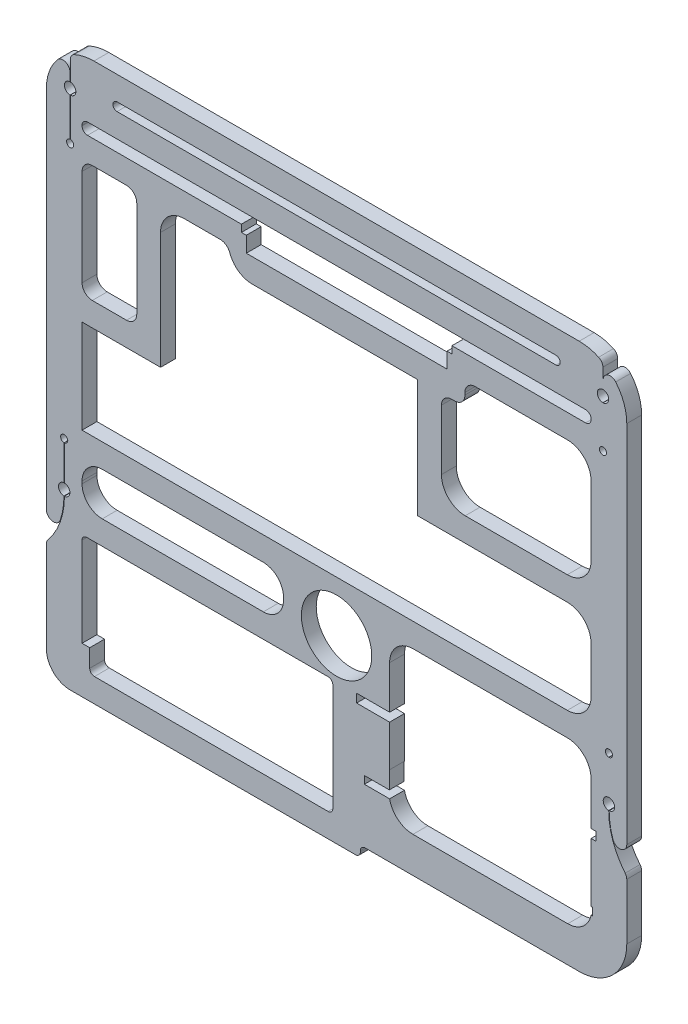
SolidWorks part; units mm, degrees
ref_plane "Front Plane" through (0, 0, 0) normal (0, 0, 1) x (1, 0, 0)
ref_plane "Top Plane" through (0, 0, 0) normal (0, 1, 0) x (1, 0, 0)
ref_plane "Right Plane" through (0, 0, 0) normal (1, 0, 0) x (0, 0, -1)
sketch "Sketch1" plane through (0, 0, 0) normal (0, 0, 1) x (1, 0, 0)
  line L0 (63.9883, 61.406) -> (63.9883, 57.596) construction
  line L1 (11.1776, 3.1158) -> (73.1542, 3.1158)
  line L2 (11.1776, 3.1158) -> (11.1776, 61.406)
  line L3 (11.1776, 61.406) -> (73.1542, 61.406)
  line L4 (73.1542, 3.1158) -> (73.1542, 61.406)
  line L5 (69.3442, 57.596) -> (14.9876, 57.596)
  line L6 (69.3442, 57.596) -> (69.3442, 6.9258)
  line L7 (69.3442, 6.9258) -> (14.9876, 6.9258)
  line L8 (14.9876, 57.596) -> (14.9876, 6.9258)
  line L9 (63.9883, 59.501) -> (18.0707, 59.501) construction
  line L10 (14.9876, 39.3805) -> (11.1776, 39.3805) construction
  line L11 (13.0826, 39.3805) -> (13.0826, 23.9527) construction
  line L12 (13.5248, 6.9258) -> (13.5248, 3.1158) construction
  line L13 (13.5248, 5.0208) -> (21.1598, 5.0208) construction
  line L14 (73.1542, 38.1916) -> (69.3442, 38.1916) construction
  line L15 (71.2492, 38.1916) -> (71.2492, 22.3321) construction
  line L16 (55.7422, 59.501) -> (30.5962, 59.501) construction
  line L19 (42.3087, 5.0208) -> (41.7626, 5.0208) construction
  line L21 (69.3442, 28.1307) -> (69.3442, 52.516) construction
  line L22 (14.9876, 47.563) -> (14.9876, 28.1307) construction
  dimension "D1" = 3.81
  dimension "D2" = 3.81
extrude "Boss-Extrude1" add sketch "Sketch1" along normal blind 1.5875
sketch "Sketch2" plane through (0, 0, 0) normal (0, 0, -1) x (-1, 0, 0)
  line L0 (-69.3442, 6.9258) -> (-69.3442, 57.596) construction
  line L1 (-69.3442, 26.6348) -> (-14.9876, 26.6348)
  line L2 (-69.3442, 26.6348) -> (-69.3442, 24.0948)
  line L3 (-69.3442, 24.0948) -> (-14.9876, 24.0948)
  line L4 (-14.9876, 26.6348) -> (-14.9876, 24.0948)
  line L5 (-14.9876, 57.596) -> (-14.9876, 6.9258) construction
  line L6 (-20.1206, 26.6348) -> (-57.8206, 26.6348) construction
  line L7 (-53.9642, 53.4304) -> (-53.9642, 51.7667)
  line L8 (-32.5266, 53.4304) -> (-32.0059, 53.4304)
  line L9 (-32.5266, 51.7667) -> (-53.9642, 51.7667) construction
  line L10 (-32.5266, 51.7667) -> (-32.5266, 53.4304) construction
  line L11 (-69.3442, 54.1924) -> (-54.4849, 54.1924)
  line L12 (-69.3442, 54.1924) -> (-69.3442, 51.6524)
  line L13 (-69.3442, 51.6524) -> (-55.8692, 51.6524)
  line L14 (-14.9876, 54.1924) -> (-14.9876, 51.6524)
  line L15 (-69.3442, 57.596) -> (-14.9876, 57.596)
  line L16 (-69.3442, 57.596) -> (-69.3442, 55.4243)
  line L17 (-69.3442, 55.4243) -> (-14.9876, 55.4243)
  line L18 (-14.9876, 57.596) -> (-14.9876, 55.4243)
  line L19 (-69.3442, 57.596) -> (-14.9876, 57.596) construction
  line L20 (-54.4849, 54.1924) -> (-54.4849, 53.4304)
  line L21 (-62.3462, 55.4243) -> (-23.9922, 55.4243) construction
  line L22 (-54.4849, 53.4304) -> (-53.9642, 53.4304)
  line L23 (-32.5266, 51.7667) -> (-53.9642, 51.7667)
  line L24 (-32.5266, 51.7667) -> (-32.5266, 53.4304)
  line L25 (-55.8692, 51.6524) -> (-55.8692, 49.2267)
  line L26 (-55.8692, 49.2267) -> (-30.6216, 49.2267)
  line L27 (-30.6216, 49.2267) -> (-30.6216, 51.6524)
  line L28 (-30.6216, 51.6524) -> (-14.9876, 51.6524)
  line L29 (-32.0059, 53.4304) -> (-32.0059, 54.1924)
  line L30 (-62.3462, 54.1924) -> (-23.9922, 54.1924) construction
  line L32 (-54.4849, 53.4304) -> (-54.4849, 54.1924) construction
  line L33 (-32.0059, 53.4304) -> (-54.4849, 53.4304) construction
  line L34 (-32.0059, 54.1924) -> (-14.9876, 54.1924)
  line L36 (-32.0059, 53.4304) -> (-32.0059, 54.1924) construction
  line L37 (-32.5266, 51.7667) -> (-32.5266, 53.4304) construction
  dimension "D1" = 2.54
  dimension "D2" = 1.905
  dimension "D3" = 2.54
  dimension "D4" = 1.905
  dimension "D5" = 2.54
extrude "Boss-Extrude2" add sketch "Sketch2" against normal up to surface (1.5875 mm away) up to face at (42.1659, 32.2609, 1.5875)
sketch "Sketch3" plane through (0, 0, 0) normal (0, 0, -1) x (-1, 0, 0)
  line L0 (-57.8206, 36.6348) -> (-50.8206, 36.6348) construction
  line L1 (-57.8206, 36.6348) -> (-50.8206, 36.6348)
  line L2 (-57.8206, 36.6348) -> (-69.3442, 36.6348)
  line L3 (-69.3442, 26.6348) -> (-69.3442, 51.6524) construction
  line L4 (-69.3442, 36.6348) -> (-69.3442, 39.1748)
  line L5 (-69.3442, 39.1748) -> (-53.3606, 39.1748)
  line L6 (-50.8206, 28.408) -> (-50.8206, 36.6348)
  line L7 (-50.8206, 28.408) -> (-50.8206, 49.2267)
  line L8 (-55.8692, 49.2267) -> (-30.6216, 49.2267) construction
  line L9 (-50.8206, 49.2267) -> (-53.3606, 49.2267)
  line L10 (-53.3606, 49.2267) -> (-53.3606, 39.1748)
  line L11 (-23.3706, 36.6348) -> (-20.1206, 36.6348) construction
  line L12 (-23.3706, 36.6348) -> (-20.1206, 36.6348)
  line L13 (-20.1206, 36.6348) -> (-14.9876, 36.6348)
  line L14 (-14.9876, 51.6524) -> (-14.9876, 26.6348) construction
  line L15 (-14.9876, 36.6348) -> (-14.9876, 39.1748)
  line L16 (-14.9876, 39.1748) -> (-20.8306, 39.1748)
  line L17 (-20.8306, 39.1748) -> (-20.8306, 51.6524)
  line L18 (-30.6216, 51.6524) -> (-14.9876, 51.6524) construction
  line L19 (-20.8306, 51.6524) -> (-23.3706, 51.6524)
  line L20 (-23.3706, 51.6524) -> (-23.3706, 36.6348)
  line L21 (-23.3706, 36.6348) -> (-16.2412, 25.8471)
  line M22 (-69.3442, 26.6348) -> (-69.3442, 51.6524)
  line M25 (-55.8692, 49.2267) -> (-30.6216, 49.2267)
  line M27 (-30.6216, 51.6524) -> (-14.9876, 51.6524)
  line M28 (-14.9876, 51.6524) -> (-14.9876, 26.6348)
  dimension "D1" = 2.54
  dimension "D2" = 2.54
  dimension "D3" = 2.54
  dimension "D4" = 2.54
extrude "Boss-Extrude3" add sketch "Sketch3" against normal up to surface (1.5875 mm away) contours L10 L5 L2 L1 L6 L7 M25 M22 | L20 L12 L13 L16 L17 M27 M28 region at (63.5824, 36.8588, 0) region at (20.9265, 42.3962, 0) up to face at (42.8855, 53.7395, 1.5875)
sketch "Sketch4" plane through (0, 0, 0) normal (0, 0, -1) x (-1, 0, 0)
  line L0 (-69.3442, 24.0948) -> (-14.9876, 24.0948) construction
  line L1 (-47.8301, 24.0948) -> (-36.5017, 24.0948)
  line L2 (-47.8301, 24.0948) -> (-47.8301, 6.9258)
  line L3 (-47.8301, 6.9258) -> (-36.5017, 6.9258)
  line L4 (-36.5017, 24.0948) -> (-36.5017, 6.9258)
  line L5 (-14.9876, 6.9258) -> (-69.3442, 6.9258) construction
  line L6 (-45.9251, 21.2246) -> (-47.8301, 21.2246) construction
  line L7 (-38.4067, 21.2246) -> (-36.5017, 21.2246) construction
  circle A0 centre (-42.1659, 21.2246) radius 3.7592 construction
  dimension "D1" = 1.905
extrude "Boss-Extrude4" add sketch "Sketch4" against normal up to surface (1.5875 mm away) up to face at (17.9091, 45.4136, 1.5875)
sketch "Sketch5" plane through (0, 0, 0) normal (0, 0, -1) x (-1, 0, 0)
  line L0 (-15.8038, 16.9715) -> (-41.7626, 16.9715) construction
  line L3 (-41.7626, 4.5128) -> (-41.7626, 16.9715) construction
  line L4 (-15.8038, 4.5128) -> (-41.7626, 4.5128) construction
  line L5 (-15.8038, 4.5128) -> (-15.8038, 16.9715) construction
  line L6 (-15.8038, 16.9715) -> (-41.7626, 16.9715)
  line L7 (-41.7626, 4.5128) -> (-41.7626, 16.9715)
  line L8 (-15.8038, 4.5128) -> (-41.7626, 4.5128)
  line L9 (-15.8038, 4.5128) -> (-15.8038, 16.9715)
  circle A0 centre (-42.1659, 21.2246) radius 3.7592 construction
  circle A1 centre (-42.1659, 21.2246) radius 3.7592
extrude "Cut-Extrude1" cut sketch "Sketch5" against normal up to surface (1.5875 mm away) up to face at (58.5871, 15.5103, 1.5875)
sketch "Sketch8" plane through (0, 0, 0) normal (0, 0, -1) x (-1, 0, 0)
  line L1 (-36.5017, 16.9715) -> (-14.9876, 16.9715)
  line L2 (-36.5017, 16.9715) -> (-36.5017, 19.5115)
  line L3 (-36.5017, 19.5115) -> (-14.9876, 19.5115)
  line L4 (-14.9876, 16.9715) -> (-14.9876, 19.5115)
  line L5 (-14.9876, 24.0948) -> (-14.9876, 6.9258) construction
  dimension "D1" = 2.54
extrude "Boss-Extrude5" add sketch "Sketch8" against normal up to surface (1.5875 mm away) up to face at (38.4067, 21.2246, 1.5875)
fillet "Fillet1" radius 5.08 3 edges at (73.1542, 3.1158, 0.7937) (11.1776, 61.406, 0.7937) (73.1542, 61.406, 0.7937)
fillet "Fillet2" radius 2.54 7 edges at (23.3706, 51.6524, 0.7937) (30.6216, 49.2267, 0.7937) (69.3442, 51.6524, 0.7937) (53.3606, 39.1748, 0.7937) (69.3442, 26.6348, 0.7937) (69.3442, 39.1748, 0.7937) (69.3442, 36.6348, 0.7937)
fillet "Fillet3" radius 1.0922 8 edges at (53.3606, 49.2267, 0.7937) (55.8692, 49.2267, 0.7937) (55.8692, 51.6524, 0.7937) (14.9876, 39.1748, 0.7937) (20.8306, 39.1748, 0.7937) (14.9876, 51.6524, 0.7937) (20.8306, 51.6524, 0.7937) (30.6216, 51.6524, 0.7937)
fillet "Fillet4" radius 0.5842 4 edges at (14.9876, 55.4243, 0.7937) (69.3442, 55.4243, 0.7937) (69.3442, 54.1924, 0.7937) (14.9876, 54.1924, 0.7937)
fillet "Fillet8" radius 2.159 4 edges at (36.5017, 19.5115, 0.7937) (36.5017, 24.0948, 0.7937) (14.9876, 24.0948, 0.7938) (14.9876, 19.5115, 0.7937)
sketch "Sketch6" plane through (0, 0, 0) normal (0, 0, -1) x (-1, 0, 0)
  line L0 (-16.6206, 28.1348) -> (-18.1206, 26.6348) construction
  line L1 (-18.1206, 36.6348) -> (-16.6206, 35.1348) construction
  line L2 (-16.6206, 35.1348) -> (-16.6206, 28.1348) construction
  line L3 (-16.6206, 28.1348) -> (-18.1206, 26.6348)
  line L4 (-18.1206, 36.6348) -> (-16.6206, 35.1348)
  line L5 (-16.6206, 35.1348) -> (-16.6206, 28.1348)
  line L6 (-18.1206, 36.6348) -> (-18.1206, 26.6348)
  circle A0 centre (-71.2492, 20.1932) radius 0.6096 construction
  circle A1 centre (-71.2492, 20.1932) radius 0.6096
  circle A4 centre (-70.6142, 57.596) radius 0.6096 construction
  circle A5 centre (-70.6142, 57.596) radius 0.6096
  circle A6 centre (-13.0826, 20.1932) radius 0.6096 construction
  circle A7 centre (-13.0826, 20.1932) radius 0.6096
  circle A10 centre (-13.7176, 57.596) radius 0.6096 construction
  circle A11 centre (-13.7176, 57.596) radius 0.6096
extrude "Cut-Extrude2" cut sketch "Sketch6" against normal up to surface (1.5875 mm away) up to face at (24.1846, 9.4701, 1.5875)
sketch "Sketch7" plane through (0, 0, 0) normal (0, 0, -1) x (-1, 0, 0)
  line L0 (-44.3026, 16.9715) -> (-69.8804, 16.9715) construction
  line L1 (-69.8804, 16.9715) -> (-69.8804, 16.0571) construction
  line L2 (-69.8804, 16.0571) -> (-44.3026, 16.0571) construction
  line L3 (-44.3026, 16.0571) -> (-44.3026, 16.9715) construction
  line L4 (-45.1366, 9.7751) -> (-69.5206, 9.7751) construction
  line L5 (-69.5206, 9.7751) -> (-69.5206, 8.9623) construction
  line L6 (-69.5206, 8.9623) -> (-45.1366, 8.9623) construction
  line L7 (-45.1366, 8.9623) -> (-45.1366, 9.7751) construction
  line L8 (-44.3026, 16.9715) -> (-69.8804, 16.9715)
  line L9 (-69.8804, 16.9715) -> (-69.8804, 16.0571)
  line L10 (-69.8804, 16.0571) -> (-44.3026, 16.0571)
  line L11 (-44.3026, 16.0571) -> (-44.3026, 16.9715)
  line L12 (-45.1366, 9.7751) -> (-69.5206, 9.7751)
  line L13 (-69.5206, 9.7751) -> (-69.5206, 8.9623)
  line L14 (-69.5206, 8.9623) -> (-45.1366, 8.9623)
  line L15 (-45.1366, 8.9623) -> (-45.1366, 9.7751)
  line L20 (-66.8536, 9.7751) -> (-47.8036, 9.7751)
  line L21 (-47.8036, 9.7751) -> (-47.8036, 11.6547)
  line L22 (-47.8036, 11.6547) -> (-66.8536, 11.6547)
  line L23 (-66.8536, 11.6547) -> (-66.8536, 9.7751)
  line L24 (-66.8536, 9.7751) -> (-47.8036, 9.7751)
  line L25 (-47.8036, 9.7751) -> (-47.8036, 11.6547)
  line L26 (-47.8036, 11.6547) -> (-66.8536, 11.6547)
  line L27 (-66.8536, 11.6547) -> (-66.8536, 9.7751)
  dimension "D1" = 0
extrude "Cut-Extrude3" cut sketch "Sketch7" against normal up to surface (1.5875 mm away) contours L14 L15 L12 L13 | L26 L27 L12 L25 | L10 L11 L8 L9 region at (57.0915, 16.5143, 0) region at (57.3286, 9.3687, 0) region at (57.3286, 10.7149, 0) up to face at (13.108, 57.596, 1.5875)
fillet "Fillet6" radius 0.508 4 edges at (41.7626, 16.9715, 0.7937) (41.7626, 4.5128, 0.7937) (15.8038, 4.5128, 0.7937) (14.9876, 16.9715, 0.7937)
sketch "Sketch9" plane through (0, 0, 1.5875) normal (0, 0, 1) x (1, 0, 0)
  line L0 (68.0742, 61.406) -> (16.2576, 61.406) construction
  line L1 (18.2896, 58.866) -> (66.0422, 58.866)
  line L2 (18.2896, 58.866) -> (18.2896, 57.9643)
  line L3 (18.2896, 57.9643) -> (66.0422, 57.9643)
  line L8 (66.0422, 58.866) -> (66.0422, 57.9643)
  line L9 (15.5718, 55.4243) -> (68.76, 55.4243) construction
  line L10 (11.1776, 56.326) -> (11.1776, 59.3208) construction
  line L11 (18.2896, 58.866) -> (11.1776, 58.866) construction
  line L13 (66.0422, 58.866) -> (73.1542, 58.866) construction
  line L14 (73.1542, 56.326) -> (73.1542, 56.8419) construction
  dimension "D1" = 2.54
  dimension "D2" = 2.54
  dimension "D3" = 7.112
extrude "Cut-Extrude4" cut sketch "Sketch9" against normal up to surface (1.5875 mm away) up to face at (57.106, 13.2916, 0)
fillet "Fillet7" radius 0.4318 4 edges at (18.2896, 57.9643, 0.7937) (18.2896, 58.866, 0.7937) (66.0422, 57.9643, 0.7937) (66.0422, 58.866, 0.7937)
fillet "Fillet9" radius 2.54 4 edges at (69.3442, 6.9258, 0.7937) (47.8301, 6.9258, 0.7937) (69.3442, 24.0948, 0.7937) (47.8301, 24.0948, 0.7937)
sketch "Sketch10" plane through (0, 0, 1.5875) normal (0, 0, 1) x (1, 0, 0)
  line L0 (42.1659, 24.9838) -> (42.1659, -13.4858) construction
  line L1 (11.1776, 3.1158) -> (44.7059, 3.1158)
  line L2 (11.1776, 3.1158) -> (11.1776, 1.9728)
  line L3 (11.1776, 1.9728) -> (44.7059, 1.9728)
  line L4 (44.7059, 3.1158) -> (44.7059, 1.9728)
  line L5 (16.3118, 4.5128) -> (41.2546, 4.5128) construction
  circle A0 centre (42.1659, 21.2246) radius 3.7592 construction
  dimension "D1" = 2.54
  dimension "D2" = 2.54
extrude "Boss-Extrude6" add sketch "Sketch10" against normal up to surface (1.5875 mm away) up to face at (42.1659, 58.4152, 0)
fillet "Fillet10" radius 2.54 1 edges at (11.1776, 1.9728, 0.7937)
fillet "Fillet11" radius 0.508 2 edges at (44.7059, 3.1158, 0.7937) (44.7059, 1.9728, 0.7937)
sketch "Sketch11" plane through (0, 0, 1.5875) normal (0, 0, 1) x (1, 0, 0)
  line L0 (13.7049, 59.0933) -> (13.7049, 58.2055) construction
  line L1 (13.7049, 56.9866) -> (13.7049, 52.8968) construction
  line L2 (13.7303, 52.8968) -> (13.7303, 56.9866) construction
  line L3 (13.7303, 58.2055) -> (13.7303, 60.2667) construction
  line L4 (70.6015, 58.2055) -> (70.6015, 60.2667) construction
  line L5 (70.6269, 56.9866) -> (70.6269, 52.8968) construction
  line L6 (70.6015, 52.8968) -> (70.6015, 56.9866) construction
  line L7 (71.2619, 24.5118) -> (71.2619, 20.8027) construction
  line L8 (71.2365, 24.5118) -> (71.2365, 20.8027) construction
  line L9 (13.0953, 24.5118) -> (13.0953, 20.8027) construction
  line L10 (13.0699, 24.5118) -> (13.0699, 20.8027) construction
  line L11 (13.7049, 59.0933) -> (13.7049, 58.2055)
  line L12 (13.7049, 56.9866) -> (13.7049, 52.8968)
  line L13 (13.7303, 52.8968) -> (13.7303, 56.9866)
  line L14 (13.7303, 58.2055) -> (13.7303, 60.2667)
  line L15 (70.6015, 58.2055) -> (70.6015, 60.2667)
  line L16 (70.6269, 56.9866) -> (70.6269, 52.8968)
  line L17 (70.6015, 52.8968) -> (70.6015, 56.9866)
  line L18 (71.2619, 24.5118) -> (71.2619, 20.8027)
  line L19 (71.2365, 24.5118) -> (71.2365, 20.8027)
  line L20 (13.0953, 24.5118) -> (13.0953, 20.8027)
  line L21 (13.0699, 24.5118) -> (13.0699, 20.8027)
  line L22 (73.1542, 8.1958) -> (73.1542, 56.326) construction
  line L23 (11.1776, 56.326) -> (11.1776, 4.5128) construction
  line L24 (73.1542, 14.1854) -> (73.1542, 17.3909)
  line L25 (11.1776, 17.3909) -> (11.1776, 14.1854)
  line L26 (70.6269, 59.0933) -> (70.6269, 58.2055) construction
  line L27 (70.6269, 59.0933) -> (70.6269, 58.2055)
  arc A0 (13.7049, 59.0933) -> (12.3579, 59.5817) centre (12.9429, 59.0933) ccw construction
  arc A1 (13.7049, 52.8968) -> (13.7303, 52.8968) centre (13.7176, 52.516) ccw construction
  arc A2 (14.1807, 60.9621) -> (13.7303, 60.2667) centre (14.4923, 60.2667) ccw construction
  arc A3 (70.6015, 60.2667) -> (70.151, 60.9621) centre (69.8395, 60.2667) ccw construction
  arc A4 (71.9738, 59.5817) -> (70.6269, 59.0933) centre (71.3889, 59.0933) ccw construction
  arc A5 (70.6015, 52.8968) -> (70.6269, 52.8968) centre (70.6142, 52.516) ccw construction
  arc A6 (71.2619, 24.5118) -> (71.2365, 24.5118) centre (71.2492, 24.8926) ccw construction
  arc A7 (71.2746, 19.5842) -> (71.6692, 17.1501) centre (78.975, 19.5836) ccw construction
  arc A8 (71.6692, 17.1501) -> (73.1542, 17.3909) centre (72.3922, 17.3909) ccw construction
  arc A9 (71.2238, 19.5842) -> (72.9814, 14.6685) centre (78.975, 19.5836) ccw construction
  arc A10 (73.1542, 14.1854) -> (72.9814, 14.6685) centre (72.3922, 14.1854) ccw construction
  arc A11 (13.0953, 24.5118) -> (13.0699, 24.5118) centre (13.0826, 24.8926) ccw construction
  arc A12 (11.3503, 14.6685) -> (13.108, 19.5842) centre (5.3567, 19.5836) ccw construction
  arc A13 (12.6625, 17.1501) -> (13.0572, 19.5842) centre (5.3567, 19.5836) ccw construction
  arc A14 (11.1776, 17.3909) -> (12.6625, 17.1501) centre (11.9396, 17.3909) ccw construction
  arc A15 (11.3503, 14.6685) -> (11.1776, 14.1854) centre (11.9396, 14.1854) ccw construction
  arc A16 (13.7049, 59.0933) -> (12.3579, 59.5817) centre (12.9429, 59.0933) ccw
  arc A17 (13.7049, 52.8968) -> (13.7303, 52.8968) centre (13.7176, 52.516) ccw
  arc A18 (14.1807, 60.9621) -> (13.7303, 60.2667) centre (14.4923, 60.2667) ccw
  arc A19 (70.6015, 60.2667) -> (70.151, 60.9621) centre (69.8395, 60.2667) ccw
  arc A20 (71.9738, 59.5817) -> (70.6269, 59.0933) centre (71.3889, 59.0933) ccw
  arc A21 (70.6015, 52.8968) -> (70.6269, 52.8968) centre (70.6142, 52.516) ccw
  arc A22 (71.2619, 24.5118) -> (71.2365, 24.5118) centre (71.2492, 24.8926) ccw
  arc A23 (71.2746, 19.5842) -> (71.6692, 17.1501) centre (78.975, 19.5836) ccw
  arc A24 (71.6692, 17.1501) -> (73.1542, 17.3909) centre (72.3922, 17.3909) ccw
  arc A25 (71.2238, 19.5842) -> (72.9814, 14.6685) centre (78.975, 19.5836) ccw
  arc A26 (73.1542, 14.1854) -> (72.9814, 14.6685) centre (72.3922, 14.1854) ccw
  arc A27 (13.0953, 24.5118) -> (13.0699, 24.5118) centre (13.0826, 24.8926) ccw
  arc A28 (11.3503, 14.6685) -> (13.108, 19.5842) centre (5.3567, 19.5836) ccw
  arc A29 (12.6625, 17.1501) -> (13.0572, 19.5842) centre (5.3567, 19.5836) ccw
  arc A30 (11.1776, 17.3909) -> (12.6625, 17.1501) centre (11.9396, 17.3909) ccw
  arc A31 (11.3503, 14.6685) -> (11.1776, 14.1854) centre (11.9396, 14.1854) ccw
  arc A32 (16.2576, 61.406) -> (11.1776, 56.326) centre (16.2576, 56.326) ccw construction
  circle A33 centre (13.7176, 57.596) radius 0.6096 construction
  arc A34 (73.1542, 56.326) -> (68.0742, 61.406) centre (68.0742, 56.326) ccw construction
  circle A35 centre (70.6142, 57.596) radius 0.6096 construction
  circle A36 centre (71.2492, 20.1932) radius 0.6096 construction
  circle A37 centre (13.0826, 20.1932) radius 0.6096 construction
  arc A38 (14.1807, 60.9621) -> (12.3579, 59.5817) centre (16.2576, 56.326) ccw
  arc A39 (13.7303, 58.2055) -> (13.7049, 58.2055) centre (13.7176, 57.596) ccw
  arc A40 (71.9738, 59.5817) -> (70.151, 60.9621) centre (68.0742, 56.326) ccw
  arc A41 (70.6015, 56.9866) -> (70.6269, 56.9866) centre (70.6142, 57.596) ccw
  arc A42 (71.2619, 20.8027) -> (71.2365, 20.8027) centre (71.2492, 20.1932) ccw
  arc A43 (13.0572, 19.5842) -> (13.108, 19.5842) centre (13.0826, 20.1932) ccw
  arc A44 (13.0953, 20.8027) -> (13.0699, 20.8027) centre (13.0826, 20.1932) ccw
  arc A45 (13.7049, 56.9866) -> (13.7303, 56.9866) centre (13.7176, 57.596) ccw
  arc A46 (71.2238, 19.5842) -> (71.2746, 19.5842) centre (71.2492, 20.1932) ccw
  arc A47 (70.6015, 56.9866) -> (70.6269, 56.9866) centre (70.6142, 57.596) ccw
  arc A48 (70.6269, 58.2055) -> (70.6015, 58.2055) centre (70.6142, 57.596) ccw
extrude "Cut-Extrude5" cut sketch "Sketch11" against normal through all contours A39 L14 A18 A38 A16 L11 | A45 L12 A17 L13 | A43 A29 A30 L25 A31 A28 | A44 L20 A27 L21 | A46 A25 A26 L24 A24 A23 | A42 L18 A22 L19 | A48 L27 A20 A40 A19 L15 | A41 L17 A21 L16 region at (13.3996, 60.0409, 1.5875) region at (13.7176, 52.9661, 1.5875) region at (70.9321, 60.0409, 1.5875) region at (70.6142, 52.9661, 1.5875) region at (71.2492, 24.5099, 1.5875) region at (13.0826, 24.5099, 1.5875) region at (72.5827, 16.1148, 1.5875) region at (11.749, 16.1148, 1.5875)
